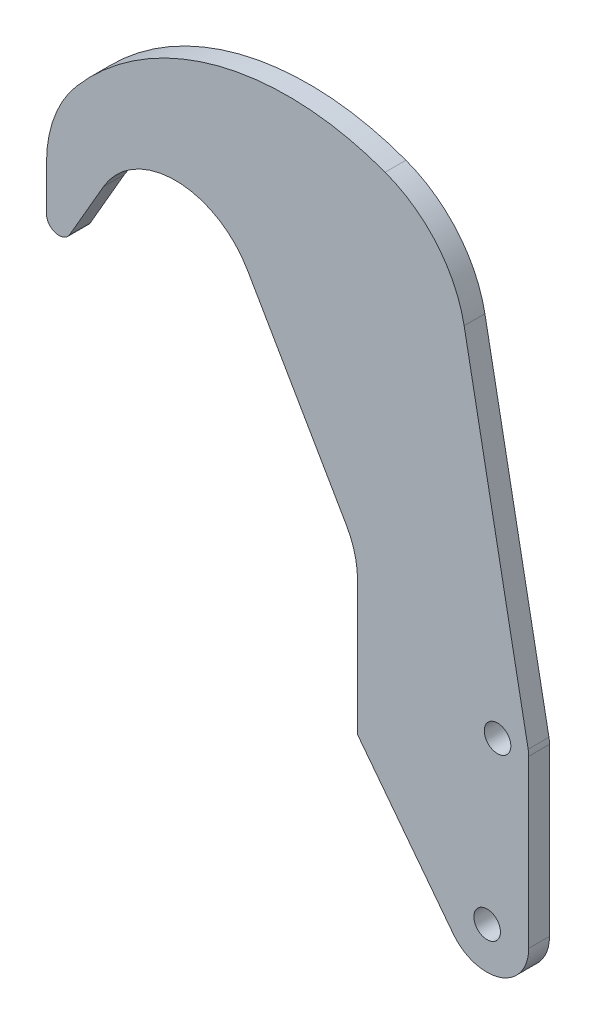
SolidWorks part; units mm, degrees
ref_plane "Front Plane" through (0, 0, 0) normal (0, 0, 1) x (1, 0, 0)
ref_plane "Top Plane" through (0, 0, 0) normal (0, 1, 0) x (1, 0, 0)
ref_plane "Right Plane" through (0, 0, 0) normal (1, 0, 0) x (0, 0, -1)
sketch "Sketch1" plane through (0, 0, 0) normal (0, 0, 1) x (1, 0, 0)
  line L0 (-10.9985, 23.8125) -> (-26.1215, -2.3812) construction
  line L1 (-15.123, -21.4313) -> (15.123, -21.4313) construction
  line L2 (26.1215, -2.3812) -> (10.9985, 23.8125) construction
  line L3 (10.9985, 23.8125) -> (26.1215, -2.3812)
  line L4 (-10.9985, 23.8125) -> (-16.1312, 14.9225)
  line L5 (-19.6859, 15.875) -> (-19.6859, 28.575)
  line L8 (53.975, -19.05) -> (53.975, -44.45)
  line L9 (47.625, -50.8) -> (47.4961, -50.8)
  line L15 (53.8902, -18.1554) -> (42.458, 41.6228)
  line L16 (27.823, -8.7312) -> (27.823, -29.2393)
  line L17 (27.823, -29.2393) -> (42.458, -48.3152)
  circle A0 centre (0, 0) radius 21.4313 construction
  arc A1 (10.9985, 23.8125) -> (-10.9985, 23.8125) centre (0, 17.4625) ccw construction
  arc A2 (-26.1215, -2.3812) -> (-15.123, -21.4313) centre (-15.123, -8.7313) ccw construction
  arc A3 (15.123, -21.4313) -> (26.1215, -2.3812) centre (15.123, -8.7312) ccw construction
  arc A4 (-10.9985, 23.8125) -> (10.9985, 23.8125) centre (0, 17.4625) cw
  arc A5 (26.1215, -2.3812) -> (27.823, -8.7312) centre (15.123, -8.7312) cw
  arc A6 (53.975, -19.05) -> (53.8902, -18.1554) centre (49.2125, -19.05) ccw
  arc A9 (-19.6859, 15.875) -> (-16.1312, 14.9225) centre (-17.7809, 15.875) ccw
  arc A10 (47.625, -50.8) -> (53.975, -44.45) centre (47.625, -44.45) ccw
  arc A11 (42.458, -48.3152) -> (47.4961, -50.8) centre (47.4961, -44.45) ccw
  circle A12 centre (47.625, -44.45) radius 2.032
  circle A15 centre (49.2125, -19.05) radius 2.032
  arc A16 (-19.6859, 28.575) -> (42.458, 41.6228) centre (17.2053, 7.3828) cw
  dimension "D2" = 12.7
  dimension "D3" = 9.525
  dimension "D1" = 42.8625
  dimension "D4" = 30
  dimension "D5" = 1.905
  dimension "D12" = 4.064
  dimension "D9" = 50.8
  dimension "D7" = 42.545
  dimension "D6" = 12.7
  dimension "D8" = 15.875
  dimension "D14" = 47.625
  dimension "D15" = 44.45
  dimension "D16" = 25.4
extrude "Boss-Extrude1" add sketch "Sketch1" along normal mid plane 3.175
fillet "Fillet1" radius 19.05 2 edges at (-19.6859, 28.575, 0) (42.458, 41.6228, 0)
